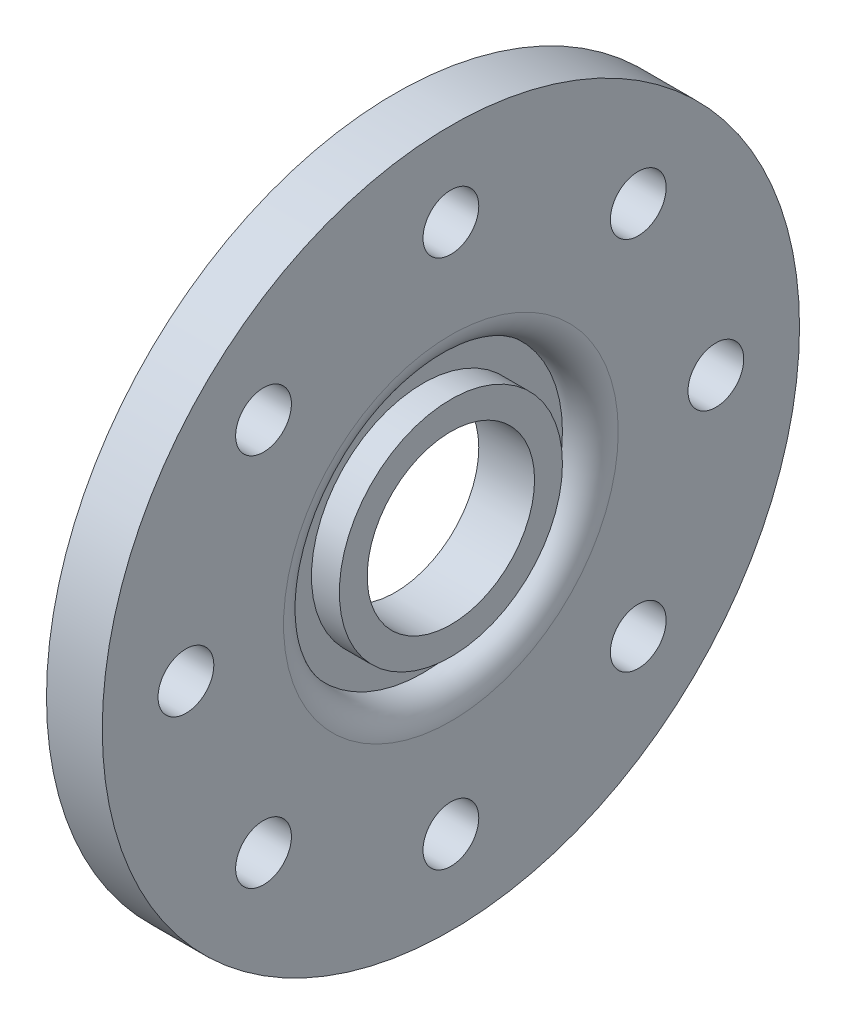
SolidWorks part; units mm, degrees
material "1060 Alloy"
ref_plane "Front Plane" through (0, 0, 0) normal (0, 0, 1) x (1, 0, 0)
ref_plane "Top Plane" through (0, 0, 0) normal (0, 1, 0) x (1, 0, 0)
ref_plane "Right Plane" through (0, 0, 0) normal (1, 0, 0) x (0, 0, -1)
sketch "Sketch1" plane through (0, 0, 0) normal (1, 0, 0) x (0, 0, -1)
  line L0 (12.5, 0) -> (9.5, 0)
  circle A0 centre (0, 0) radius 12.5
  circle A1 centre (0, 0) radius 3
  circle A2 centre (9.5, 0) radius 1
  circle A3 centre (6.7175, -6.7175) radius 1
  circle A4 centre (0, -9.5) radius 1
  circle A5 centre (-6.7175, -6.7175) radius 1
  circle A6 centre (-9.5, 0) radius 1
  circle A7 centre (-6.7175, 6.7175) radius 1
  circle A8 centre (0, 9.5) radius 1
  circle A9 centre (6.7175, 6.7175) radius 1
  point P24 (0, 0)
  dimension "D1" = 25
  dimension "D2" = 6
  dimension "D4" = 2
  dimension "D3" = 3
  dimension "D5" = 8
extrude "Boss-Extrude1" add sketch "Sketch1" along normal blind 2 contours A2 A0 A9 A8 A7 A6 A5 A4 A3 A1 region at (0, 0, 12.1464)
sketch "Sketch2" plane through (2, 0, 0) normal (1, 0, 0) x (0, 0, -1)
  circle A0 centre (0, 0) radius 4
  circle A1 centre (0, 0) radius 5
  dimension "D1" = 1
  dimension "D2" = 8
extrude "Cut-Extrude1" cut sketch "Sketch2" against normal blind 1
fillet "Fillet1" radius 1 1 edges at (2, 0, -5)
